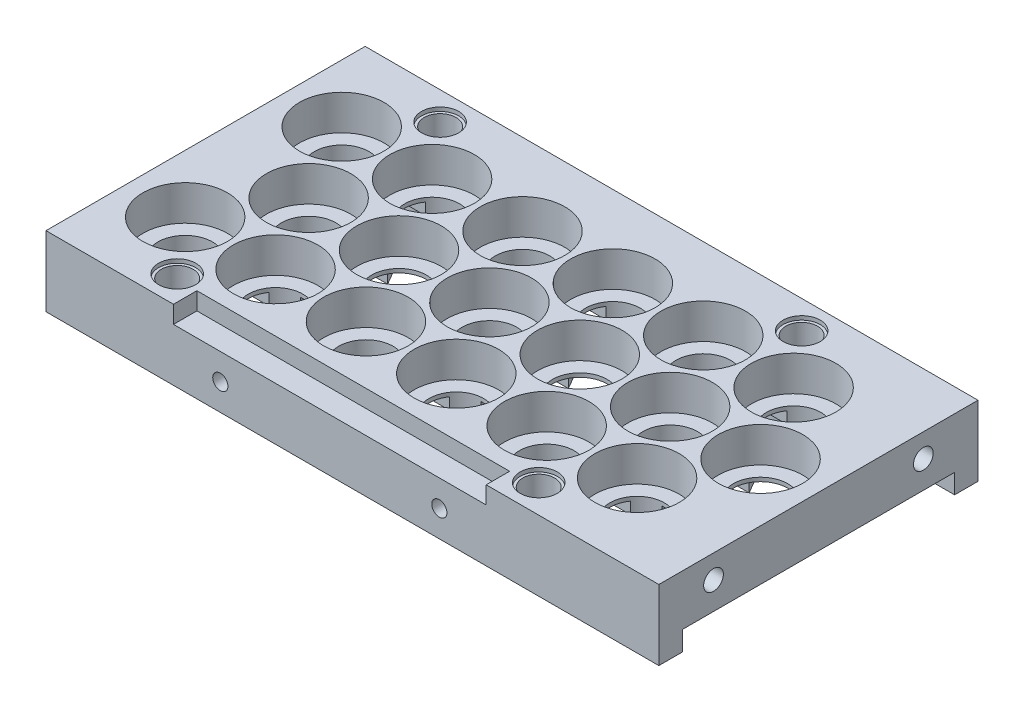
SolidWorks part; units mm, degrees
ref_plane "Front Plane" through (0, 0, 0) normal (0, 0, 1) x (1, 0, 0)
ref_plane "Top Plane" through (0, 0, 0) normal (0, 1, 0) x (1, 0, 0)
ref_plane "Right Plane" through (0, 0, 0) normal (1, 0, 0) x (0, 0, -1)
sketch "Sketch1" plane through (0, 0, 0) normal (0, 1, 0) x (1, 0, 0)
  line L0 (0, 0) -> (11.575, -20.0485) construction
  line L1 (11.575, -20.0485) -> (0, -40.097) construction
  line L2 (0, 0) -> (11.575, 0) construction
  line L3 (11.575, 0) -> (11.575, -20.0485) construction
  line L4 (11.575, -20.0485) -> (11.575, -40.097) construction
  line L5 (11.575, -40.097) -> (0, -40.097) construction
  line L6 (0, 0) -> (23.15, 0) construction
  line L7 (0, 0) -> (23.15, 0) construction
  line L8 (-14.825, -60.922) -> (142.15, -60.922)
  line L9 (-14.825, -60.922) -> (-14.825, 20.825)
  line L10 (-14.825, 20.825) -> (142.15, 20.825)
  line L11 (142.15, -60.922) -> (142.15, 20.825)
  circle A0 centre (0, 0) radius 10.825
  circle A1 centre (11.575, -20.0485) radius 10.825
  circle A2 centre (0, -40.097) radius 10.825
  circle A3 centre (23.15, 0) radius 10.825
  circle A4 centre (34.725, -20.0485) radius 10.825
  circle A5 centre (23.15, -40.097) radius 10.825
  circle A6 centre (46.3, 0) radius 10.825
  circle A7 centre (57.875, -20.0485) radius 10.825
  circle A8 centre (46.3, -40.097) radius 10.825
  circle A9 centre (69.45, 0) radius 10.825
  circle A10 centre (81.025, -20.0485) radius 10.825
  circle A11 centre (69.45, -40.097) radius 10.825
  circle A12 centre (92.6, 0) radius 10.825
  circle A13 centre (104.175, -20.0485) radius 10.825
  circle A14 centre (92.6, -40.097) radius 10.825
  circle A15 centre (115.75, 0) radius 10.825
  circle A16 centre (127.325, -20.0485) radius 10.825
  circle A17 centre (115.75, -40.097) radius 10.825
  circle A18 centre (0, 0) radius 7
  circle A19 centre (11.575, -20.0485) radius 7
  circle A20 centre (0, -40.097) radius 7
  circle A21 centre (23.15, 0) radius 7
  circle A22 centre (34.725, -20.0485) radius 7
  circle A23 centre (23.15, -40.097) radius 7
  circle A24 centre (46.3, 0) radius 7
  circle A25 centre (57.875, -20.0485) radius 7
  circle A26 centre (46.3, -40.097) radius 7
  circle A27 centre (69.45, 0) radius 7
  circle A28 centre (81.025, -20.0485) radius 7
  circle A29 centre (69.45, -40.097) radius 7
  circle A30 centre (92.6, 0) radius 7
  circle A31 centre (104.175, -20.0485) radius 7
  circle A32 centre (92.6, -40.097) radius 7
  circle A33 centre (115.75, 0) radius 7
  circle A34 centre (127.325, -20.0485) radius 7
  circle A35 centre (115.75, -40.097) radius 7
  dimension "D3" = 21.65
  dimension "D11" = 14
  dimension "D1" = 60
  dimension "D2" = 60
  dimension "D4" = 1.5
  dimension "D6" = 23.15
  dimension "D7" = 4
  dimension "D8" = 4
  dimension "D9" = 10
  dimension "D10" = 10
  dimension "D13" = 23.15
  dimension "D5" = 6
  dimension "D12" = 6
extrude "Boss-Extrude2" add sketch "Sketch1" along normal blind 11 and the other way blind 2 contours L8 L11 L10 L9 A17 A16 A15 A14 A13 A12 A11 A10 A9 A8 A7 A6 A5 A4 A3 A2 A1 A0 region at (-13.0551, 0, 20.0485)
extrude "Boss-Extrude3" add sketch "Sketch1<3>" along normal blind 2 and the other way blind 2 contours A0 A18 | A3 A21 | A6 A24 | A9 A27 | A12 A30 | A15 A33 | A1 A19 | A4 A22 | A7 A25 | A10 A28 | A13 A31 | A16 A34 | A17 A35 | A14 A32 | A11 A29 | A8 A26 | A5 A23 | A2 A20 region at (-10.5188, 0, 0) region at (1.0562, 0, 20.0485) region at (-10.5188, 0, 40.097) region at (12.6312, 0, 0) region at (24.2062, 0, 20.0485) region at (12.6312, 0, 40.097) region at (35.7812, 0, 0) region at (47.3562, 0, 20.0485) region at (35.7812, 0, 40.097) region at (58.9312, 0, 0) region at (70.5062, 0, 20.0485) region at (58.9312, 0, 40.097) region at (82.0812, 0, 0) region at (93.6562, 0, 20.0485) region at (82.0812, 0, 40.097) region at (105.2312, 0, 0) region at (116.8062, 0, 20.0485) region at (105.2312, 0, 40.097)
sketch "Sketch1<3>" plane through (0, 0, 0) normal (0, 1, 0) x (1, 0, 0) same geometry as "Sketch1"
sketch "Sketch9" plane through (0, 11, 0) normal (0, 1, 0) x (1, 0, 0)
  line L0 (11.575, -60.922) -> (11.575, 20.825)
  line L1 (-14.825, 20.825) -> (142.15, 20.825) construction
  line L2 (104.175, 20.825) -> (104.175, -60.922)
  line L3 (-14.825, -60.922) -> (142.15, -60.922) construction
  circle A0 centre (11.575, 13.625) radius 4.0767
  circle A1 centre (11.575, -53.722) radius 4.0767
  circle A2 centre (104.175, -53.722) radius 4.0767
  circle A3 centre (104.175, 13.625) radius 4.0767
  point P0 (11.575, 13.625)
  point P7 (11.575, -20.0485)
  point P15 (104.175, -20.0485)
  point P20 (104.175, 13.625)
  point P21 (104.175, -53.722)
  point P22 (11.575, -53.722)
  dimension "D5" = 8.1534
  dimension "D1" = 7.2
  dimension "D4" = 7.2
extrude "Cut-Extrude3" cut sketch "Sketch9" against normal up to next contours A2 | A1 | A0 | A3
sketch "Sketch10" plane through (0, 11, 0) normal (0, 1, 0) x (1, 0, 0)
  circle A0 centre (11.575, 13.625) radius 4.7625
  circle A1 centre (104.175, 13.625) radius 4.7625
  circle A2 centre (104.175, -53.722) radius 4.7625
  circle A3 centre (11.575, -53.722) radius 4.7625
  dimension "D1" = 9.525
extrude "Cut-Extrude4" cut sketch "Sketch10" against normal blind 1
sketch "Sketch13" plane through (0, -2, 0) normal (0, -1, 0) x (1, 0, 0)
  line L0 (142.15, 60.922) -> (142.15, -20.825) construction
  line L5 (3.575, 53.722) -> (3.575, 60.922)
  line L8 (-14.825, 60.922) -> (142.15, 60.922) construction
  line L9 (3.575, 60.922) -> (19.575, 60.922)
  line L10 (19.575, 60.922) -> (19.575, 53.722)
  line L12 (57.875, 20.0485) -> (57.875, -20.825) construction
  line L13 (-14.825, -20.825) -> (142.15, -20.825) construction
  line L14 (11.575, 20.0485) -> (127.325, 20.0485) construction
  line L16 (96.175, 60.922) -> (96.175, 53.722)
  line L17 (112.175, 60.922) -> (96.175, 60.922)
  line L18 (112.175, 53.722) -> (112.175, 60.922)
  line L19 (-14.825, 60.922) -> (142.15, 60.922)
  line L20 (-14.825, 60.922) -> (-14.825, 54.922)
  line L21 (-14.825, 54.922) -> (142.15, 54.922)
  line L22 (142.15, 60.922) -> (142.15, 54.922)
  line L23 (142.15, -20.825) -> (142.15, -14.825)
  line L24 (-14.825, -14.825) -> (142.15, -14.825)
  line L25 (-14.825, -20.825) -> (-14.825, -14.825)
  line L26 (-14.825, -20.825) -> (142.15, -20.825)
  line L27 (112.175, -13.625) -> (112.175, -20.825)
  line L28 (112.175, -20.825) -> (96.175, -20.825)
  line L29 (96.175, -20.825) -> (96.175, -13.625)
  line L32 (19.575, -20.825) -> (19.575, -13.625)
  line L33 (3.575, -20.825) -> (19.575, -20.825)
  line L34 (3.575, -13.625) -> (3.575, -20.825)
  circle A4 centre (11.575, 53.722) radius 6.5
  circle A5 centre (11.575, 53.722) radius 8
  circle A6 centre (104.175, 53.722) radius 8
  circle A7 centre (104.175, 53.722) radius 6.5
  circle A8 centre (104.175, -13.625) radius 6.5
  circle A9 centre (104.175, -13.625) radius 8
  circle A10 centre (11.575, -13.625) radius 8
  circle A11 centre (11.575, -13.625) radius 6.5
  line M15 (142.15, 60.922) -> (-14.825, 60.922)
  line M16 (-14.825, 60.922) -> (-14.825, -20.825)
  line M17 (-14.825, -20.825) -> (142.15, -20.825)
  line M18 (142.15, -20.825) -> (142.15, 60.922)
  dimension "D1" = 13
  dimension "D2" = 16
  dimension "D3" = 6
extrude "Boss-Extrude7" add sketch "Sketch13" along normal blind 5 contours L21 L5 M16 M15 | A5 L5 L21 M15 | A5 L21 L10 M15 | L10 L21 L16 M15 | L21 A5 L19 A4 | A5 L21 A4 | L21 A6 L16 M15 | L21 A7 A6 L19 | L21 A7 A6 | A6 L21 L18 M15 | L18 L21 M18 M15 | A9 L24 L29 L26 | L28 A9 L24 A8 | A9 L26 L27 L24 | L24 L27 L26 M18 | L32 L26 L29 L24 | L24 A9 A8 | L34 L24 M16 M17 | L26 A10 L24 L34 | L24 A11 A10 | L24 A11 A10 L33 | L24 A10 L26 L32 region at (3.7817, -2, 54.3098) region at (-5.625, -2, 57.922) region at (4.8282, -2, 59.2567) region at (5.2714, -2, 58.3681) region at (18.3218, -2, 59.2567) region at (57.875, -2, 57.922) region at (-5.625, -2, -17.825) region at (97.4282, -2, 59.2567) region at (4.8282, -2, -19.1597) region at (96.3817, -2, 54.3098) region at (97.8714, -2, 58.3681) region at (3.7817, -2, -14.2128) region at (4.4261, -2, -14.9942) region at (110.9218, -2, 59.2567) region at (127.1625, -2, 57.922) region at (18.3218, -2, -19.1597) region at (57.875, -2, -17.825) region at (97.4282, -2, -19.1597) region at (127.1625, -2, -17.825) region at (96.3817, -2, -14.2128) region at (97.0261, -2, -14.9942) region at (110.9218, -2, -19.1597)
sketch "Sketch2" plane through (0, -2, 0) normal (0, -1, 0) x (1, 0, 0)
  line L0 (0, 40.097) -> (11.575, 20.0485) construction
  line L1 (3.4641, 42.097) -> (15.0391, 22.0485)
  line L2 (-3.4641, 38.097) -> (8.1109, 18.0485)
  line L3 (11.575, 20.0485) -> (0, 0) construction
  line L4 (15.0391, 18.0485) -> (3.4641, -2)
  line L5 (8.1109, 22.0485) -> (-3.4641, 2)
  line L6 (19.6859, 38.097) -> (31.2609, 18.0485)
  line L7 (26.6141, 42.097) -> (38.1891, 22.0485)
  line L8 (31.2609, 22.0485) -> (19.6859, 2)
  line L9 (38.1891, 18.0485) -> (26.6141, -2)
  line L10 (23.15, 40.097) -> (34.725, 20.0485) construction
  line L11 (34.725, 20.0485) -> (23.15, 0) construction
  line L12 (42.8359, 38.097) -> (54.4109, 18.0485)
  line L13 (49.7641, 42.097) -> (61.3391, 22.0485)
  line L14 (54.4109, 22.0485) -> (42.8359, 2)
  line L15 (61.3391, 18.0485) -> (49.7641, -2)
  line L16 (46.3, 40.097) -> (57.875, 20.0485) construction
  line L17 (57.875, 20.0485) -> (46.3, 0) construction
  line L18 (65.9859, 38.097) -> (77.5609, 18.0485)
  line L19 (72.9141, 42.097) -> (84.4891, 22.0485)
  line L20 (77.5609, 22.0485) -> (65.9859, 2)
  line L21 (84.4891, 18.0485) -> (72.9141, -2)
  line L22 (69.45, 40.097) -> (81.025, 20.0485) construction
  line L23 (81.025, 20.0485) -> (69.45, 0) construction
  line L24 (89.1359, 38.097) -> (100.7109, 18.0485)
  line L25 (96.0641, 42.097) -> (107.6391, 22.0485)
  line L26 (100.7109, 22.0485) -> (89.1359, 2)
  line L27 (107.6391, 18.0485) -> (96.0641, -2)
  line L28 (92.6, 40.097) -> (104.175, 20.0485) construction
  line L29 (104.175, 20.0485) -> (92.6, 0) construction
  line L30 (112.2859, 38.097) -> (123.8609, 18.0485)
  line L31 (119.2141, 42.097) -> (130.7891, 22.0485)
  line L32 (123.8609, 22.0485) -> (112.2859, 2)
  line L33 (130.7891, 18.0485) -> (119.2141, -2)
  line L34 (115.75, 40.097) -> (127.325, 20.0485) construction
  line L35 (127.325, 20.0485) -> (115.75, 0) construction
  line L36 (-3.4641, 38.097) -> (19.6859, 38.097) construction
  line L37 (0, 40.097) -> (115.75, 40.097) construction
  line L38 (0, 44.097) -> (115.75, 44.097)
  line L39 (0, 36.097) -> (115.75, 36.097)
  line L40 (11.575, 20.0485) -> (127.325, 20.0485) construction
  line L41 (11.575, 24.0485) -> (127.325, 24.0485)
  line L42 (11.575, 16.0485) -> (127.325, 16.0485)
  line L43 (0, 0) -> (115.75, 0) construction
  line L44 (0, 4) -> (115.75, 4)
  line L45 (0, -4) -> (115.75, -4)
  arc A0 (3.4641, 42.097) -> (-3.4641, 38.097) centre (0, 40.097) ccw
  arc A1 (8.1109, 18.0485) -> (15.0391, 22.0485) centre (11.575, 20.0485) ccw
  arc A2 (15.0391, 18.0485) -> (8.1109, 22.0485) centre (11.575, 20.0485) ccw
  arc A3 (-3.4641, 2) -> (3.4641, -2) centre (0, 0) ccw
  arc A4 (26.6141, 42.097) -> (19.6859, 38.097) centre (23.15, 40.097) ccw
  arc A5 (31.2609, 18.0485) -> (38.1891, 22.0485) centre (34.725, 20.0485) ccw
  arc A6 (38.1891, 18.0485) -> (31.2609, 22.0485) centre (34.725, 20.0485) ccw
  arc A7 (19.6859, 2) -> (26.6141, -2) centre (23.15, 0) ccw
  arc A8 (49.7641, 42.097) -> (42.8359, 38.097) centre (46.3, 40.097) ccw
  arc A9 (54.4109, 18.0485) -> (61.3391, 22.0485) centre (57.875, 20.0485) ccw
  arc A10 (61.3391, 18.0485) -> (54.4109, 22.0485) centre (57.875, 20.0485) ccw
  arc A11 (42.8359, 2) -> (49.7641, -2) centre (46.3, 0) ccw
  arc A12 (72.9141, 42.097) -> (65.9859, 38.097) centre (69.45, 40.097) ccw
  arc A13 (77.5609, 18.0485) -> (84.4891, 22.0485) centre (81.025, 20.0485) ccw
  arc A14 (84.4891, 18.0485) -> (77.5609, 22.0485) centre (81.025, 20.0485) ccw
  arc A15 (65.9859, 2) -> (72.9141, -2) centre (69.45, 0) ccw
  arc A16 (96.0641, 42.097) -> (89.1359, 38.097) centre (92.6, 40.097) ccw
  arc A17 (100.7109, 18.0485) -> (107.6391, 22.0485) centre (104.175, 20.0485) ccw
  arc A18 (107.6391, 18.0485) -> (100.7109, 22.0485) centre (104.175, 20.0485) ccw
  arc A19 (89.1359, 2) -> (96.0641, -2) centre (92.6, 0) ccw
  arc A20 (119.2141, 42.097) -> (112.2859, 38.097) centre (115.75, 40.097) ccw
  arc A21 (123.8609, 18.0485) -> (130.7891, 22.0485) centre (127.325, 20.0485) ccw
  arc A22 (130.7891, 18.0485) -> (123.8609, 22.0485) centre (127.325, 20.0485) ccw
  arc A23 (112.2859, 2) -> (119.2141, -2) centre (115.75, 0) ccw
  arc A24 (0, 44.097) -> (0, 36.097) centre (0, 40.097) ccw
  arc A25 (115.75, 36.097) -> (115.75, 44.097) centre (115.75, 40.097) ccw
  arc A26 (11.575, 24.0485) -> (11.575, 16.0485) centre (11.575, 20.0485) ccw
  arc A27 (127.325, 16.0485) -> (127.325, 24.0485) centre (127.325, 20.0485) ccw
  arc A28 (0, 4) -> (0, -4) centre (0, 0) ccw
  arc A29 (115.75, -4) -> (115.75, 4) centre (115.75, 0) ccw
  point P3 (5.7875, 30.0727)
  point P8 (5.7875, 10.0242)
  point P18 (28.9375, 30.0727)
  point P25 (28.9375, 10.0242)
  point P34 (52.0875, 30.0727)
  point P39 (52.0875, 10.0242)
  point P48 (75.2375, 30.0727)
  point P53 (75.2375, 10.0242)
  point P62 (98.3875, 30.0727)
  point P67 (98.3875, 10.0242)
  point P76 (121.5375, 30.0727)
  point P81 (121.5375, 10.0242)
  point P91 (57.875, 40.097)
  point P96 (69.45, 20.0485)
  point P103 (57.875, 0)
  dimension "D1" = 8
  dimension "D3" = 23.15
  dimension "D4" = 8
  dimension "D5" = 8
  dimension "D6" = 8
extrude "Cut-Extrude1" cut sketch "Sketch2" against normal blind 3 contours L1 L39 L38 | L42 L8 L6 L41 | L13 L39 L38 | L18 L41 L19 L39 | L25 L39 L38 | L42 L32 L30 L41 | L42 L20 L18 L41 | L45 L44 L4 | L45 L44 L15 | L45 L44 L27 | L44 L21 L42 L20 | L39 L13 | L39 L25 | L39 L19 | L41 L6 | L44 L4 | L44 L15 | L44 L21 | L44 L27 | L41 L30 | L32 L42 | L41 L18 | L20 L42 | L44 L9 L42 L8 | L8 L42 | L39 L7 | L39 L1 | A23 L32 L44 L45 | L30 L41 L31 | L42 L32 L33 | L6 L41 L7 L39 | A7 L9 L44 L8 region at (12.1489, -2, 40.3471) region at (0.784, -2, 39.6443) region at (21.9471, -2, 20.0485) region at (28.9375, -2, 30.0727) region at (23.8945, -2, 39.601) region at (30.3235, -2, 22.793) region at (58.4489, -2, 40.3471) region at (47.0445, -2, 39.601) region at (30.3235, -2, 17.304) region at (70.1945, -2, 39.601) region at (0.784, -2, 0.4527) region at (28.9375, -2, 10.0242) region at (104.7489, -2, 40.3471) region at (93.3445, -2, 39.601) region at (12.1489, -2, -0.2501) region at (23.8945, -2, 0.496) region at (68.2471, -2, 20.0485) region at (75.2375, -2, 30.0727) region at (76.6235, -2, 22.793) region at (121.4671, -2, 30.6948) region at (58.4489, -2, -0.2501) region at (47.0445, -2, 0.496) region at (76.6235, -2, 17.304) region at (114.5471, -2, 20.0485) region at (70.1945, -2, 0.496) region at (75.2375, -2, 10.0242) region at (121.4671, -2, 9.4022) region at (122.9235, -2, 22.793) region at (104.7489, -2, -0.2501) region at (93.3445, -2, 0.496) region at (122.9235, -2, 17.304)
sketch "Sketch19" plane through (0, 0, 60.922) normal (0, 0, 1) x (1, 0, 0)
  line L0 (11.575, 11) -> (104.175, 11)
  line L1 (-14.825, 11) -> (142.15, 11) construction
  line L2 (97.925, 11) -> (17.825, 11)
  line L3 (17.825, 11) -> (97.925, 11)
  line L4 (17.825, 11) -> (17.825, 6.525)
  line L5 (97.925, 11) -> (97.925, 6.525)
  line L6 (17.825, 6.525) -> (97.925, 6.525)
  point P5 (57.875, 11)
  point P9 (57.875, 11)
  dimension "D1" = 92.6
  dimension "D2" = 26.4
  dimension "D3" = 80.1
  dimension "D4" = 4.475
extrude "Cut-Extrude6" cut sketch "Sketch19" against normal blind 6 contours L4 L6 L5 L0 region at (57.875, 8.7625, 60.922)
sketch "Sketch20" plane through (0, 0, 60.922) normal (0, 0, 1) x (1, 0, 0)
  line L0 (29.825, 6.525) -> (85.925, 6.525)
  line L1 (29.825, 6.525) -> (29.825, -0.2375)
  line L2 (85.925, 6.525) -> (85.925, -0.2375)
  line L3 (29.825, -0.2375) -> (85.925, -0.2375)
  line L4 (29.825, 6.525) -> (17.825, 6.525) construction
  line L5 (85.925, 6.525) -> (97.925, 6.525) construction
  line L6 (57.875, 6.525) -> (57.875, -7)
  line L9 (142.15, -7) -> (-14.825, -7) construction
  circle A0 centre (29.825, -0.2375) radius 1.9431
  circle A1 centre (85.925, -0.2375) radius 1.9431
  point P9 (57.875, -0.2375)
  dimension "D2" = 3.8862
  dimension "D1" = 12
extrude "Cut-Extrude7" cut sketch "Sketch20" against normal blind 3.8862 contours L1 A0 L3 | L3 A0 L1 | L3 A1 L2 | L2 A1 L3 region at (30.6497, 0.5872, 60.922) region at (29.5501, -0.5124, 60.922) region at (86.1999, -0.5124, 60.922) region at (85.1003, 0.5872, 60.922)
sketch "Sketch22" plane through (142.15, 0, 0) normal (1, 0, 0) x (0, 0, -1)
  line L0 (-46.922, 5) -> (-60.922, 5)
  line L1 (-60.922, 11) -> (-60.922, -7) construction
  line L2 (6.825, 5) -> (20.825, 5)
  line L3 (20.825, 11) -> (20.825, -7) construction
  line L4 (-46.922, 5) -> (-46.922, 11)
  line L5 (-60.922, 11) -> (20.825, 11) construction
  line L6 (6.825, 5) -> (6.825, 11)
  circle A0 centre (-46.922, 5) radius 2.525
  circle A1 centre (6.825, 5) radius 2.525
  dimension "D1" = 5.05
  dimension "D2" = 14
  dimension "D3" = 6
extrude "Cut-Extrude8" cut sketch "Sketch22" against normal blind 3.81 contours L0 A0 L4 | L4 A0 L0 | L6 A1 L2 | L2 A1 L6 region at (142.15, 4.6428, 46.5648) region at (142.15, 6.0716, 47.9936) region at (142.15, 6.0716, -7.8966) region at (142.15, 4.6428, -6.4678)
sketch "Sketch26" plane through (0, -2, 0) normal (0, -1, 0) x (1, 0, 0)
  line L0 (57.875, -14.825) -> (57.875, -4) construction
  line L1 (132.15, -9.4125) -> (57.875, -9.4125) construction
  line L2 (57.875, -9.4125) -> (-10.825, -9.4125) construction
  line L3 (11.575, 20.0485) -> (82.7573, 20.0485)
  line L4 (57.875, 49.5095) -> (-10.825, 49.5095) construction
  line L5 (132.15, 49.5095) -> (57.875, 49.5095) construction
  line L6 (57.875, 54.922) -> (57.875, 44.097) construction
  line L7 (19.4845, 54.922) -> (96.2655, 54.922) construction
  line L8 (52.0446, 44.097) -> (63.7054, 44.097) construction
  line L9 (-14.825, 54.922) -> (-14.825, -14.825) construction
  line L10 (142.15, 54.922) -> (142.15, -14.825) construction
  circle A0 centre (132.15, -9.4125) radius 1.9431
  circle A1 centre (57.875, -9.4125) radius 1.9431
  circle A2 centre (-10.825, -9.4125) radius 1.9431
  circle A3 centre (-10.825, 49.5095) radius 1.9431
  circle A4 centre (57.875, 49.5095) radius 1.9431
  circle A5 centre (132.15, 49.5095) radius 1.9431
  point P18 (11.575, 20.0485)
  point P20 (-9.1212, 49.8947)
  point P21 (35.3168, 27.0234)
  point P23 (131.2051, 49.7584)
  point P24 (35.3168, 49.1)
  point P25 (35.0358, 43.9566)
  point P26 (57.875, 54.922)
  point P29 (57.875, 43.1405)
  point P30 (57.875, 44.097)
  dimension "D1" = 3.8862
  dimension "D2" = 4
  dimension "D3" = 10
extrude "Cut-Extrude9" cut sketch "Sketch26" against normal blind 5 contours A3 | A4 | A5 | A2 | A1 | A0
equation "\"hole_diameter\"= 21.65"
equation "\"D3@Sketch1\"=\"hole_diameter\""
equation "\"cell_spacing\"= 1.5"
equation "\"D4@Sketch1\"=\"cell_spacing\""
equation "\"D6@Sketch1\"=\"hole_diameter\"+\"cell_spacing\""
equation "\"len_spacing\"= 4"
equation "\"D7@Sketch1\"=\"len_spacing\""
equation "\"D8@Sketch1\"=\"len_spacing\""
equation "\"wid_spacing\"= 10"
equation "\"D9@Sketch1\"=\"wid_spacing\""
equation "\"D10@Sketch1\"=\"wid_spacing\""
equation "\"nipple\"= 14"
equation "\"D11@Sketch1\"=\"nipple\""
equation "\"D13@Sketch1\"=\"hole_diameter\"+\"cell_spacing\""
equation "\"channel\"= 8"
equation "\"D1@Sketch2\"=\"channel\""
equation "\"D3@Sketch2\"=\"hole_diameter\"+\"cell_spacing\""
equation "\"D4@Sketch2\"=\"channel\""
equation "\"D5@Sketch2\"=\"channel\""
equation "\"D6@Sketch2\"=\"channel\""
equation "\"lip\"= 6"
equation "\"lip_height\"= 1"
equation "\"outer_fillet\"=6"
equation "\"insert_placement\"= 7.2"
equation "\"D4@Sketch9\"=\"insert_placement\""
equation "\"D1@Sketch9\"=\"insert_placement\""
equation "\"heat_insert_diameter\"=8.1534"
equation "\"D5@Sketch9\"=\"heat_insert_diameter\""
equation "\"heat_insert_lip_diameter\"=9.525"
equation "\"D1@Sketch10\"=\"heat_insert_lip_diameter\""
equation "\"bolt_head_diameter\"=13"
equation "\"D1@Sketch13\"=\"bolt_head_diameter\""
equation "\"D2@Sketch13\"=\"bolt_head_diameter\"+3"
equation "\"D3@Sketch13\"=\"lip\""
equation "\"small_heat_insert\"= .153in"
equation "\"bdm_cut_depth\"=6"
equation "\"D1@Cut-Extrude6\"=\"bdm_cut_depth\""
equation "\"D1@Cut-Extrude7\"=\"small_heat_insert\""
equation "\"D2@Sketch20\"=\"small_heat_insert\""
equation "\"heat_insert_depth\"= .15in"
equation "\"D1@Cut-Extrude8\"=\"heat_insert_depth\""
equation "\"D1@Sketch26\"=\"small_heat_insert\""
equation "\"heat_insert_space\"=6"
equation "\"heat_insert\"=5.5"
